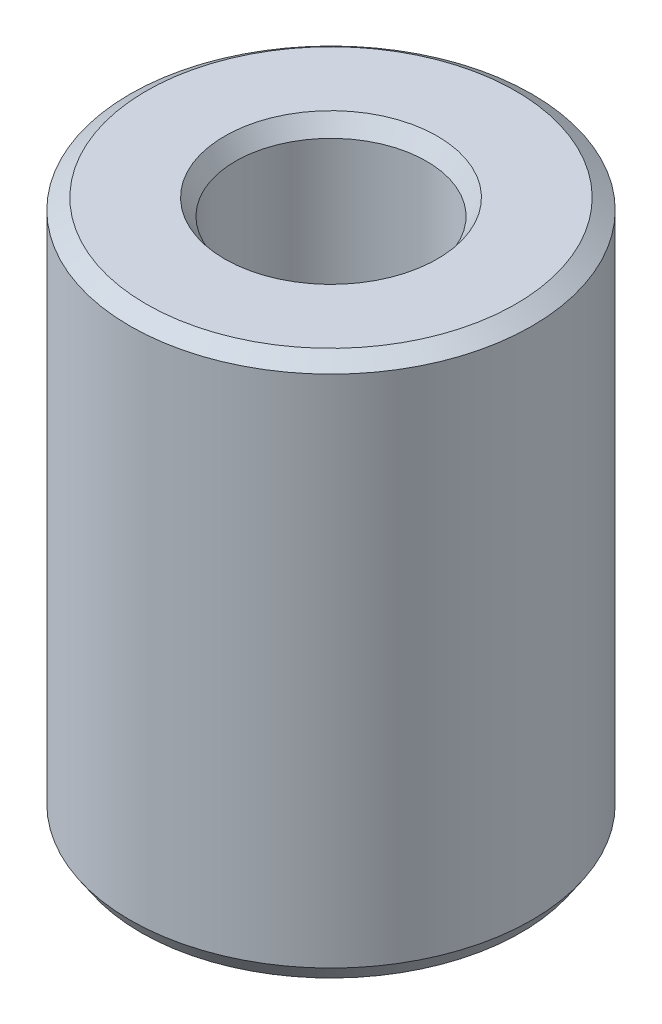
SolidWorks part; units mm, degrees
ref_plane "Front Plane" through (0, 0, 0) normal (0, 0, 1) x (1, 0, 0)
ref_plane "Top Plane" through (0, 0, 0) normal (0, 1, 0) x (1, 0, 0)
ref_plane "Right Plane" through (0, 0, 0) normal (1, 0, 0) x (0, 0, -1)
sketch "Sketch1" plane through (0, 0, 0) normal (0, 1, 0) x (1, 0, 0)
  circle A0 centre (0, 0) radius 10
  dimension "SLEEVE_OD" = 20
extrude "Boss-Extrude1" add sketch "Sketch1" along normal blind 26.9456
sketch "Sketch2" plane through (0, 0, 0) normal (0, 1, 0) x (1, 0, 0)
  circle A0 centre (0, 0) radius 4.7543
  dimension "BORE_D" = 9.5085
extrude "Cut-Extrude1" cut sketch "Sketch2" along normal through all
chamfer "Chamfer1" distance 0.5407 angle 56.266 4 edges at (0, 26.9456, 4.7543) (0, 0, 4.7543) (0, 0, 10) (0, 26.9456, 10) first distance on face at (0, 26.9456, 4.7543) first distance on face at (0, 0, 4.7543) first distance on face at (0, 26.9456, 10)
